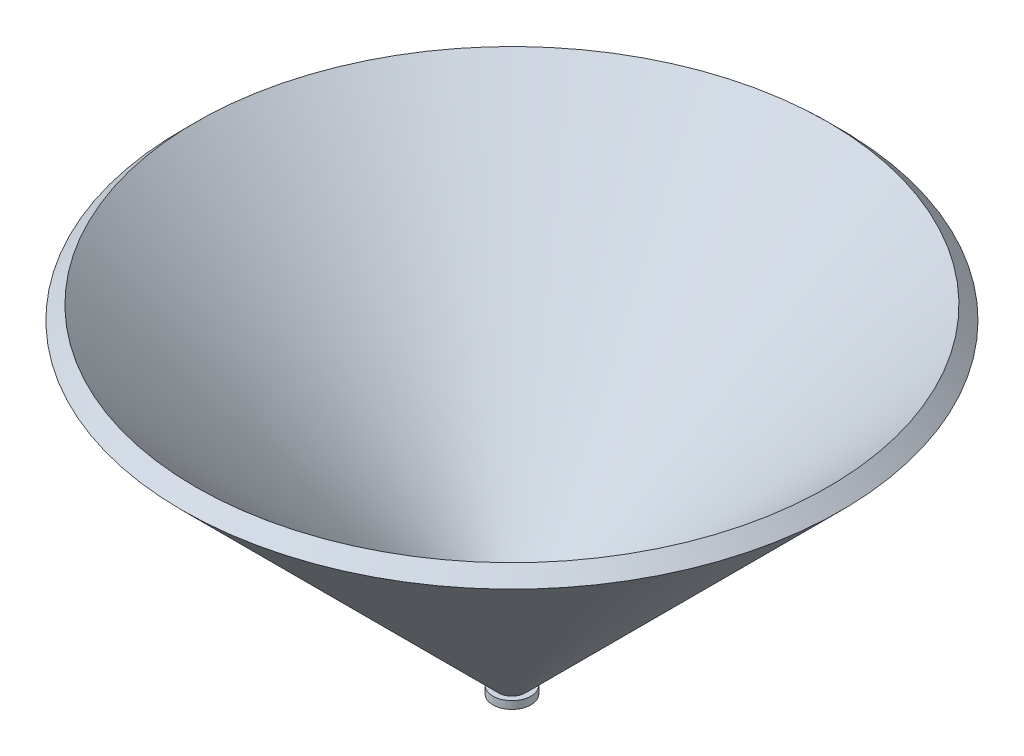
SolidWorks part; units mm, degrees
ref_plane "Front Plane" through (0, 0, 0) normal (0, 0, 1) x (1, 0, 0)
ref_plane "Top Plane" through (0, 0, 0) normal (0, 1, 0) x (1, 0, 0)
ref_plane "Right Plane" through (0, 0, 0) normal (1, 0, 0) x (0, 0, -1)
sketch "Sketch1" plane through (0, 0, 0) normal (0, 1, 0) x (1, 0, 0)
  circle A2 centre (0, 0) radius 6.35
  dimension "D1" = 12.7
extrude "Boss-Extrude1" add sketch "Sketch1" along normal blind 2.54
sketch "Sketch2" plane through (0, 0, 0) normal (1, 0, 0) x (0, 0, -1)
  line L0 (0, 2.54) -> (107.7631, 110.3031) construction
  line L1 (6.35, 2.54) -> (-6.35, 2.54) construction
  line L2 (105.518, 112.5481) -> (110.0081, 108.058)
  line L3 (110.0081, 108.058) -> (4.4901, 2.54)
  line L4 (0, 2.54) -> (0, 7.0301)
  line L5 (0, 7.0301) -> (105.518, 112.5481)
  line L7 (0, 2.54) -> (4.4901, 2.54)
  line L9 (0, 2.54) -> (0, 0) construction
  point P7 (107.7631, 110.3031)
  dimension "D1" = 45
  dimension "D2" = 152.4
  dimension "D3" = 6.35
extrude "Boss-Extrude2" add sketch "Sketch2" along normal mid plane 6.35
sketch "Sketch3" plane through (0, 0, 0) normal (0, -1, 0) x (1, 0, 0)
  circle A0 centre (0, 0) radius 1.27
  dimension "D1" = 2.54
extrude "Cut-Extrude7" cut sketch "Sketch3" against normal through all
revolve "Revolve3" add sketch "Sketch2<4>" angle 360 about L9
sketch "Sketch2<4>" plane through (0, 0, 0) normal (1, 0, 0) x (0, 0, -1) same geometry as "Sketch2"
